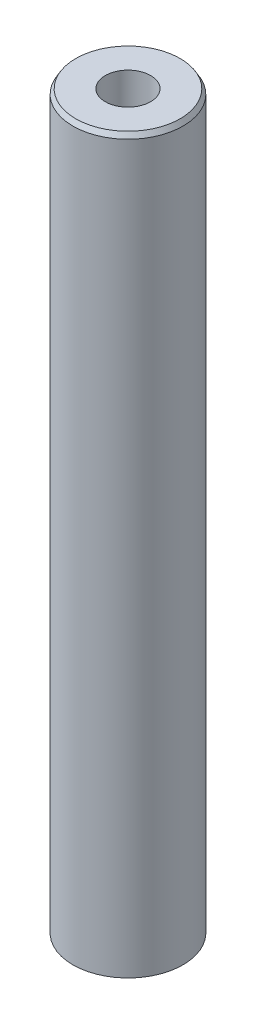
SolidWorks part; units mm, degrees
ref_plane "Front Plane" through (0, 0, 0) normal (0, 0, 1) x (1, 0, 0)
ref_plane "Top Plane" through (0, 0, 0) normal (0, 1, 0) x (1, 0, 0)
ref_plane "Right Plane" through (0, 0, 0) normal (1, 0, 0) x (0, 0, -1)
sketch "Sketch1" plane through (0, 0, 0) normal (0, 1, 0) x (1, 0, 0)
  circle A0 centre (0, 0) radius 45
  dimension "SHAFT_OD" = 90
extrude "Boss-Extrude1" add sketch "Sketch1" along normal blind 600
sketch "Sketch2" plane through (0, 0, 0) normal (0, 1, 0) x (1, 0, 0)
  circle A0 centre (0, 0) radius 18.5573
  dimension "BORE_D" = 37.1146
extrude "Cut-Extrude1" cut sketch "Sketch2" along normal through all
chamfer "Chamfer1" distance 4.0241 angle 30 2 edges at (0, 600, 45) (0, 0, 45) first distance on face at (0, 600, 45) first distance on face at (0, 0, 18.5573)
